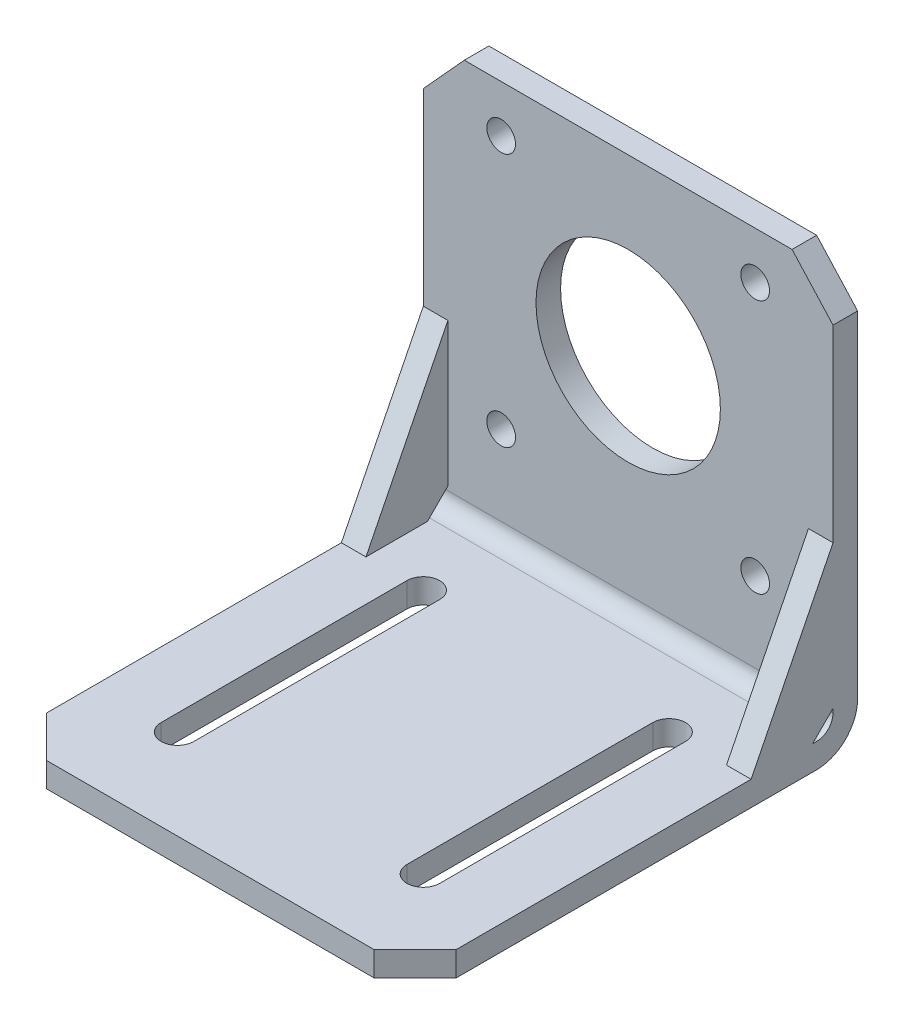
SolidWorks part; units mm, degrees
material "Acier non allié"
ref_plane "Plan de face" through (0, 0, 0) normal (0, 0, 1) x (1, 0, 0)
ref_plane "Plan de dessus" through (0, 0, 0) normal (0, 1, 0) x (1, 0, 0)
ref_plane "Plan de droite" through (0, 0, 0) normal (1, 0, 0) x (0, 0, -1)
sketch "Esquisse1" plane through (0, 0, 0) normal (0, 0, 1) x (1, 0, 0)
  line L0 (0, 0) -> (0, 50000) construction
  line L1 (-20, 51.5) -> (20, 51.5)
  line L2 (20, 51.5) -> (25, 46)
  line L3 (25, 46) -> (25, 0)
  line L4 (25, 0) -> (-25, 0)
  line L5 (15.5, 45.75) -> (15.5, 14.75) construction
  line L6 (-15.5, 30.25) -> (15.5, 30.25) construction
  line L7 (-15.5, 45.75) -> (-15.5, 14.75) construction
  line L8 (-25, 46) -> (-25, 0)
  line L9 (-20, 51.5) -> (-25, 46)
  line L10 (-15.5, 45.75) -> (15.5, 45.75) construction
  line L11 (-15.5, 14.75) -> (15.5, 14.75) construction
  circle A0 centre (0, 30.25) radius 11.25
  circle A1 centre (15.5, 45.75) radius 1.75
  circle A2 centre (15.5, 14.75) radius 1.75
  circle A3 centre (-15.5, 14.75) radius 1.75
  circle A4 centre (-15.5, 45.75) radius 1.75
  point P23 (0, 0)
  point P25 (0, 51.5)
  dimension "D3" = 3.5
  dimension "D4" = 3.5
  dimension "D5" = 22.5
  dimension "D1" = 51.5
  dimension "D2" = 46
  dimension "D6" = 31
  dimension "D7" = 21.25
  dimension "D8" = 40
  dimension "D9" = 50
extrude "Boss.-Extru.1" add sketch "Esquisse1" along normal blind 3
sketch "Esquisse2" plane through (0, 0, 0) normal (0, -1, 0) x (1, 0, 0)
  line L0 (0, 0) -> (0, 50000) construction
  line L1 (-20, 54) -> (20, 54)
  line L2 (25, 0) -> (25, 49)
  line L3 (25, 49) -> (20, 54)
  line L4 (-25, 0) -> (25, 0) construction
  line L5 (15, 54) -> (15, 0) construction
  line L6 (15, 43) -> (15, 13) construction
  line L7 (17, 43) -> (17, 13)
  line L8 (13, 43) -> (13, 13)
  line L9 (-25, 0) -> (25, 0)
  line L10 (-15, 54) -> (-15, 0) construction
  line L11 (-25, 0) -> (-25, 49)
  line L12 (-25, 49) -> (-20, 54)
  line L13 (-15, 43) -> (-15, 13) construction
  line L14 (-17, 43) -> (-17, 13)
  line L15 (-13, 43) -> (-13, 13)
  arc A0 (17, 43) -> (13, 43) centre (15, 43) ccw
  arc A1 (13, 13) -> (17, 13) centre (15, 13) ccw
  arc A2 (-17, 43) -> (-13, 43) centre (-15, 43) cw
  arc A3 (-13, 13) -> (-17, 13) centre (-15, 13) cw
  point P14 (15, 28)
  point P19 (15, 45)
  point P20 (15, 11)
  point P25 (0, 54)
  point P27 (-15, 28)
  dimension "D1" = 54
  dimension "D2" = 5
  dimension "D3" = 4
  dimension "D4" = 15
  dimension "D5" = 34
  dimension "D6" = 9
  dimension "D7" = 40
extrude "Boss.-Extru.2" add sketch "Esquisse2" against normal blind 3
fillet "Congé1" radius 2 1 edges at (0, 3, 3)
fillet "Congé2" radius 5 1 edges at (0, 0, 0)
sketch "Esquisse3" plane through (-25, 0, 0) normal (-1, 0, 0) x (0, 0, 1)
  line L0 (3, 46) -> (3, 5) construction
  line L1 (49, 3) -> (5, 3) construction
  line L2 (3, 23) -> (3, 3)
  line L3 (13, 3) -> (3, 3)
  line L4 (3, 23) -> (13, 3)
  line L5 (3, 5.5) -> (5.5, 3)
  point P0 (3, 3)
  point P2 (0, 0)
  point P6 (13.2858, 3)
  point P11 (3, 23.4199)
  line M5 (49, 3) -> (5, 3)
  dimension "D1" = 20
  dimension "D2" = 10
  dimension "D3" = 2.5
  dimension "D4" = 2.5
extrude "Boss.-Extru.3" add sketch "Esquisse3" against normal blind 3 contours L2 L5 L4 M5 region at (-25, 9.8548, 6.414)
extrude "Boss.-Extru.4" add sketch "Esquisse3<3>" along normal blind 3 from surface contours L2 L5 L4 M5 region at (-25, 9.8548, 6.414) starting at face at (25, 13.3188, 14.0688)
sketch "Esquisse3<3>" plane through (-25, 0, 0) normal (-1, 0, 0) x (0, 0, 1) same geometry as "Esquisse3"
